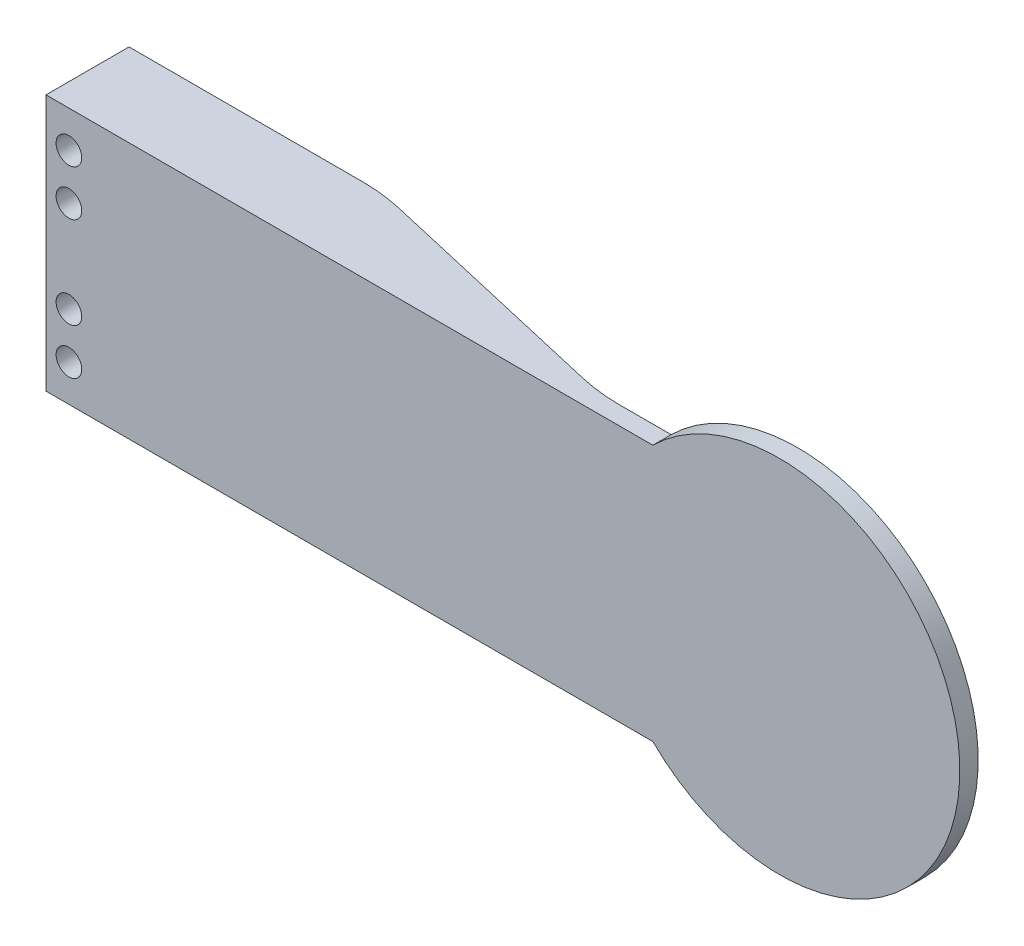
SolidWorks part; units mm, degrees
ref_plane "Front Plane" through (0, 0, 0) normal (0, 0, 1) x (1, 0, 0)
ref_plane "Top Plane" through (0, 0, 0) normal (0, 1, 0) x (1, 0, 0)
ref_plane "Right Plane" through (0, 0, 0) normal (1, 0, 0) x (0, 0, -1)
sketch "Sketch1" plane through (0, 0, 0) normal (0, 0, 1) x (1, 0, 0)
  line L1 (0, 0) -> (15, 0)
  line L2 (0, 0) -> (0, 28)
  line L3 (0, 28) -> (15, 28)
  line L4 (15, 0) -> (15, 28)
  dimension "D1" = 28
  dimension "D2" = 15
extrude "Boss-Extrude1" add sketch "Sketch1" along normal blind 9.06
sketch "Sketch2" plane through (0, 0, 9.06) normal (0, 0, 1) x (1, 0, 0)
  circle A0 centre (2.5, 24) radius 1.4 construction
  circle A1 centre (2.5, 19) radius 1.4 construction
  circle A2 centre (2.5, 9) radius 1.4 construction
  circle A3 centre (2.5, 4) radius 1.4 construction
  circle A4 centre (2.5, 24) radius 1.4
  circle A5 centre (2.5, 19) radius 1.4
  circle A6 centre (2.5, 9) radius 1.4
  circle A7 centre (2.5, 4) radius 1.4
extrude "Cut-Extrude1" cut sketch "Sketch2" against normal blind 26
sketch "Sketch3" plane through (15, 0, 0) normal (1, 0, 0) x (0, 0, -1)
  line L0 (-9.06, 0) -> (0, 0) construction
  line L1 (-9.06, 28) -> (-7.06, 28)
  line L2 (-9.06, 28) -> (-9.06, 0)
  line L3 (-9.06, 0) -> (-7.06, 0)
  line L4 (-7.06, 28) -> (-7.06, 0)
  dimension "D1" = 2
extrude "Boss-Extrude2" add sketch "Sketch3" along normal blind 85
chamfer "Chamfer1" distance 10 angle 77 1 edges at (15, 14, 7.06) first distance on face at (15, 14, 3.53)
sketch "Sketch4" plane through (0, 0, 9.06) normal (0, 0, 1) x (1, 0, 0)
  circle A0 centre (80.035, 14) radius 19.675 construction
  circle A1 centre (80.035, 14) radius 19.675
extrude "Boss-Extrude3" add sketch "Sketch4" against normal blind 2
sketch "Sketch5" plane through (0, 0, 7.06) normal (0, 0, -1) x (-1, 0, 0)
  line L6 (-58.3148, 28) -> (-66.2109, 28)
  line L7 (-93.8591, 28) -> (-100, 28)
  line L8 (-100, 28) -> (-100, 0)
  line L9 (-100, 0) -> (-93.8591, 0)
  line L10 (-66.2109, 0) -> (-58.3148, 0)
  line L11 (-58.3148, 0) -> (-58.3148, 28)
  line L12 (-58.3148, 28) -> (-66.2109, 28)
  line L13 (-93.8591, 28) -> (-100, 28)
  line L14 (-100, 28) -> (-100, 0)
  line L15 (-100, 0) -> (-93.8591, 0)
  line L16 (-66.2109, 0) -> (-58.3148, 0)
  line L17 (-58.3148, 0) -> (-58.3148, 28)
  circle A0 centre (-80.035, 14) radius 19.675 construction
  circle A1 centre (-80.035, 14) radius 19.675
  arc A4 (-66.2109, 28) -> (-93.8591, 28) centre (-80.035, 14) ccw
  arc A5 (-93.8591, 0) -> (-66.2109, 0) centre (-80.035, 14) ccw
  arc A6 (-66.2109, 28) -> (-93.8591, 28) centre (-80.035, 14) ccw
  arc A7 (-93.8591, 0) -> (-66.2109, 0) centre (-80.035, 14) ccw
  line M11 (-93.8591, 28) -> (-100, 28)
  line M12 (-100, 28) -> (-100, 0)
  line M13 (-100, 0) -> (-93.8591, 0)
  dimension "D1" = 0
extrude "Cut-Extrude3" cut sketch "Sketch5" against normal blind 2 contours A1 M11 M12 M13 region at (99.9967, 14, 7.06)
fillet "Fillet1" radius 20 2 edges at (58.3148, 14, 7.06) (27.7345, 14, 0)
